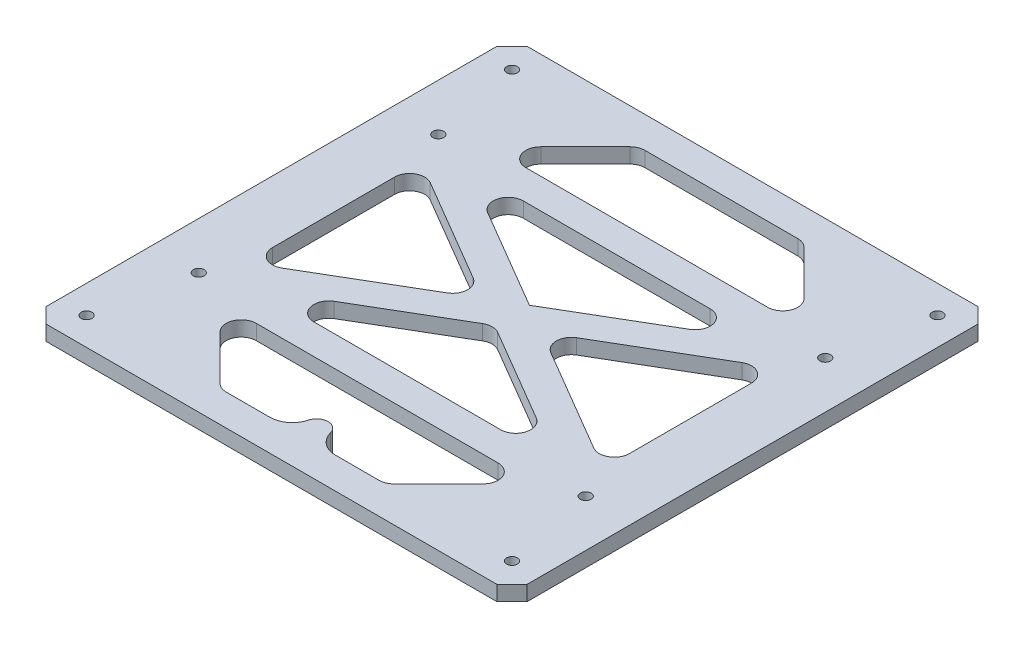
SolidWorks part; units mm, degrees
ref_plane "Front Plane" through (0, 0, 0) normal (0, 0, 1) x (1, 0, 0)
ref_plane "Top Plane" through (0, 0, 0) normal (0, 1, 0) x (1, 0, 0)
ref_plane "Right Plane" through (0, 0, 0) normal (1, 0, 0) x (0, 0, -1)
sketch "Sketch1" plane through (0, 0, 0) normal (0, 1, 0) x (1, 0, 0)
  line L0 (0, 196.85) -> (6.35, 203.2)
  line L1 (6.35, 0) -> (196.85, 0)
  line L2 (0, 6.35) -> (0, 196.85)
  line L3 (6.35, 203.2) -> (196.85, 203.2)
  line L4 (203.2, 6.35) -> (203.2, 196.85)
  line L5 (196.85, 203.2) -> (203.2, 196.85)
  line L6 (196.85, 0) -> (203.2, 6.35)
  line L7 (0, 6.35) -> (6.35, 0)
  point P0 (0, 0)
  point P1 (203.2, 203.2)
  point P2 (0, 203.2)
  point P3 (203.2, 0)
  dimension "D1" = 203.2
  dimension "D2" = 203.2
extrude "Boss-Extrude1" add sketch "Sketch1" along normal blind 6.35
sketch "Sketch3" plane through (0, 6.35, 0) normal (0, 1, 0) x (1, 0, 0)
  line L0 (6.35, 0) -> (196.85, 0) construction
  line L1 (0, 196.85) -> (0, 6.35) construction
  line L2 (203.2, 6.35) -> (203.2, 196.85) construction
  line L3 (196.85, 203.2) -> (6.35, 203.2) construction
  circle A0 centre (11.7373, 11.7373) radius 2.286
  circle A1 centre (191.4627, 11.7373) radius 2.286
  circle A2 centre (191.4627, 191.4627) radius 2.286
  circle A3 centre (11.7373, 191.4627) radius 2.286
  dimension "D1" = 2
  dimension "D3" = 4.572
  dimension "D4" = 11.7373
  dimension "D5" = 11.7373
  dimension "D6" = 11.7373
  dimension "D7" = 11.7373
  dimension "D8" = 11.7373
  dimension "D2" = 2
extrude "Cut-Extrude2" cut sketch "Sketch3" against normal through all
sketch "Sketch4" plane through (0, 6.35, 0) normal (0, 1, 0) x (1, 0, 0)
  line L0 (0, 196.85) -> (0, 6.35) construction
  line L1 (19.8692, 152.1955) -> (183.3308, 152.1955) construction
  line L2 (19.8692, 152.1955) -> (19.8692, 51.0045) construction
  line L3 (19.8692, 51.0045) -> (183.3308, 51.0045) construction
  line L4 (183.3308, 152.1955) -> (183.3308, 51.0045) construction
  line L5 (196.85, 203.2) -> (6.35, 203.2) construction
  line L6 (16.6942, 140.0403) -> (66.6884, 190.0345)
  line L7 (136.5116, 190.0345) -> (66.6884, 190.0345)
  line L8 (136.5116, 190.0345) -> (186.5058, 140.0403)
  line L9 (186.5058, 63.1597) -> (136.5116, 13.1655)
  line L10 (186.5058, 140.0403) -> (186.5058, 63.1597)
  line L11 (136.5116, 13.1655) -> (66.6884, 13.1655)
  line L12 (66.6884, 13.1655) -> (16.6942, 63.1597)
  line L13 (16.6942, 63.1597) -> (16.6942, 140.0403)
  circle A0 centre (19.8692, 152.1955) radius 2.286
  circle A1 centre (183.3308, 152.1955) radius 2.286
  circle A2 centre (183.3308, 51.0045) radius 2.286
  circle A3 centre (19.8692, 51.0045) radius 2.286
  point P6 (0, 101.6)
  point P7 (19.8692, 101.6)
  point P10 (101.6, 203.2)
  point P11 (101.6, 152.1955)
  dimension "D3" = 4.572
  dimension "D5" = 6.35
  dimension "D7" = 6.35
  dimension "D1" = 163.4617
  dimension "D2" = 101.1911
  dimension "D4" = 6.35
  dimension "D6" = 6.35
  dimension "D8" = 6.35
extrude "Cut-Extrude3" cut sketch "Sketch4" against normal through all
sketch "Sketch5" plane through (0, 6.35, 0) normal (0, 1, 0) x (1, 0, 0)
  line L0 (19.8692, 51.0045) -> (183.3308, 51.0045) construction
  line L1 (183.3308, 51.0045) -> (183.3308, 152.1955) construction
  line L2 (183.3308, 152.1955) -> (19.8692, 152.1955) construction
  line L3 (19.8692, 152.1955) -> (19.8692, 51.0045) construction
  line L4 (189.6808, 158.5455) -> (13.5192, 158.5455)
  line L5 (13.5192, 158.5455) -> (13.5192, 44.6545)
  line L6 (13.5192, 44.6545) -> (189.6808, 44.6545)
  line L7 (189.6808, 44.6545) -> (189.6808, 158.5455)
  line L8 (141.0736, 145.8455) -> (62.1264, 145.8455)
  line L9 (26.2192, 127.3922) -> (26.2192, 75.8078)
  line L10 (62.1264, 57.3545) -> (141.0736, 57.3545)
  line L11 (176.9808, 75.8078) -> (176.9808, 127.3922)
  line L12 (26.2192, 57.3545) -> (176.9808, 145.8455) construction
  line L13 (176.9808, 57.3545) -> (26.2192, 145.8455) construction
  line L14 (58.912, 69.1808) -> (98.3856, 92.3502)
  line L15 (167.4165, 70.3314) -> (123.4744, 96.1237)
  line L16 (35.7835, 70.3314) -> (79.7256, 96.1237)
  line L17 (144.288, 69.1808) -> (104.8144, 92.3502)
  line L18 (180.1952, 62.8308) -> (29.4335, 151.3219) construction
  line L19 (173.7665, 51.8781) -> (23.0048, 140.3692) construction
  line L20 (23.0048, 62.8308) -> (173.7665, 151.3219) construction
  line L21 (29.4335, 51.8781) -> (180.1952, 140.3692) construction
  line L22 (26.2192, 57.3545) -> (176.9808, 57.3545) construction
  line L23 (176.9808, 57.3545) -> (176.9808, 145.8455) construction
  line L24 (176.9808, 145.8455) -> (26.2192, 145.8455) construction
  line L25 (26.2192, 145.8455) -> (26.2192, 57.3545) construction
  line L26 (79.7256, 107.0763) -> (35.7835, 132.8686)
  line L27 (101.6, 108.963) -> (144.288, 134.0192)
  line L28 (123.4744, 107.0763) -> (167.4165, 132.8686)
  line L29 (101.6, 108.963) -> (58.912, 134.0192)
  circle A0 centre (183.3308, 51.0045) radius 2.286 construction
  circle A1 centre (183.3308, 152.1955) radius 2.286 construction
  circle A2 centre (19.8692, 152.1955) radius 2.286 construction
  circle A3 centre (19.8692, 51.0045) radius 2.286 construction
  circle A4 centre (183.3308, 51.0045) radius 2.286
  circle A5 centre (183.3308, 152.1955) radius 2.286
  circle A6 centre (19.8692, 152.1955) radius 2.286
  circle A7 centre (19.8692, 51.0045) radius 2.286
  arc A8 (58.912, 134.0192) -> (62.1264, 145.8455) centre (62.1264, 139.4955) cw
  arc A9 (144.288, 134.0192) -> (141.0736, 145.8455) centre (141.0736, 139.4955) ccw
  arc A10 (167.4165, 132.8686) -> (176.9808, 127.3922) centre (170.6308, 127.3922) cw
  arc A11 (123.4744, 107.0763) -> (123.4744, 96.1237) centre (126.6888, 101.6) ccw
  arc A12 (167.4165, 70.3314) -> (176.9808, 75.8078) centre (170.6308, 75.8078) ccw
  arc A13 (144.288, 69.1808) -> (141.0736, 57.3545) centre (141.0736, 63.7045) cw
  arc A14 (104.8144, 92.3502) -> (98.3856, 92.3502) centre (101.6, 86.8739) ccw
  arc A15 (79.7256, 107.0763) -> (79.7256, 96.1237) centre (76.5112, 101.6) cw
  arc A16 (35.7835, 132.8686) -> (26.2192, 127.3922) centre (32.5692, 127.3922) ccw
  arc A17 (35.7835, 70.3314) -> (26.2192, 75.8078) centre (32.5692, 75.8078) cw
  arc A18 (58.912, 69.1808) -> (62.1264, 57.3545) centre (62.1264, 63.7045) ccw
  dimension "D5" = 6.35
  dimension "D1" = 6.35
  dimension "D3" = 6.35
  dimension "D2" = 6.35
  dimension "D4" = 6.35
extrude "Boss-Extrude2" add sketch "Sketch5" against normal up to surface (6.35 mm away) up to face at (183.3308, 0, -149.9095)
fillet "Fillet1" radius 6.35 8 edges at (136.5116, 3.175, -190.0345) (66.6884, 3.175, -190.0345) (35.1994, 3.175, -158.5455) (168.0006, 3.175, -158.5455) (66.6884, 3.175, -13.1655) (35.1994, 3.175, -44.6545) (136.5116, 3.175, -13.1655) (168.0006, 3.175, -44.6545)
sketch "Sketch6" plane through (0, 6.35, 0) normal (0, 1, 0) x (1, 0, 0)
  line L0 (6.35, 0) -> (196.85, 0) construction
  line L1 (69.3186, 13.1655) -> (133.8814, 13.1655) construction
  line L2 (87.7184, 13.1655) -> (115.4816, 13.1655)
  circle A0 centre (101.6, 19.05) radius 2.286 construction
  arc A1 (106.2681, 20.2742) -> (96.9319, 20.2742) centre (101.6, 19.05) ccw
  arc A2 (87.7184, 13.1655) -> (96.9319, 20.2742) centre (87.7184, 22.6905) ccw
  arc A3 (106.2681, 20.2742) -> (115.4816, 13.1655) centre (115.4816, 22.6905) ccw
  point P7 (101.6, 0)
  dimension "D1" = 19.05
  dimension "D2" = 4.572
  dimension "D3" = 2.54
  dimension "D4" = 19.05
extrude "Boss-Extrude3" add sketch "Sketch6" against normal up to surface (6.35 mm away) up to face at (101.6, 0, -26.9283)
sketch "Sketch8" plane through (0, 0, 0) normal (0, 1, 0) x (1, 0, 0)
  circle A0 centre (101.6, 19.05) radius 4.826
  circle A1 centre (101.6, 19.05) radius 2.286
  arc A2 (106.2681, 20.2742) -> (96.9319, 20.2742) centre (101.6, 19.05) ccw construction
  dimension "D1" = 4.572
extrude "Boss-Extrude4" add sketch "Sketch8" against normal blind 6.35
